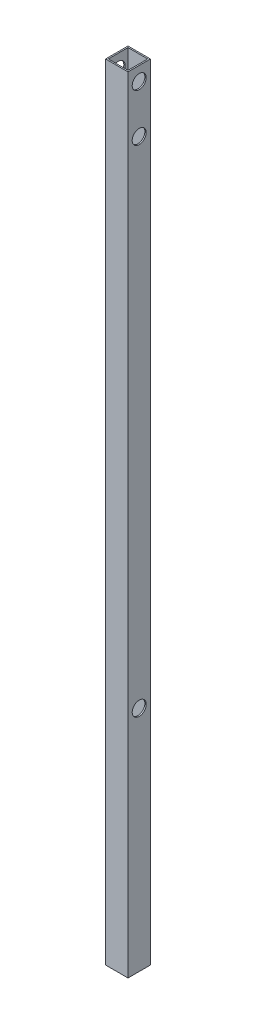
SolidWorks part; units mm, degrees
ref_plane "Front Plane" through (0, 0, 0) normal (0, 0, 1) x (1, 0, 0)
ref_plane "Top Plane" through (0, 0, 0) normal (0, 1, 0) x (1, 0, 0)
ref_plane "Right Plane" through (0, 0, 0) normal (1, 0, 0) x (0, 0, -1)
sketch "Sketch1" plane through (0, 0, 0) normal (0, 1, 0) x (1, 0, 0)
  line L1 (-59.3551, 50.3766) -> (-33.9551, 50.3766)
  line L2 (-59.3551, 50.3766) -> (-59.3551, 24.9766)
  line L3 (-59.3551, 24.9766) -> (-33.9551, 24.9766)
  line L4 (-33.9551, 50.3766) -> (-33.9551, 24.9766)
  line L5 (-57.8311, 48.8526) -> (-35.4791, 48.8526)
  line L6 (-57.8311, 48.8526) -> (-57.8311, 26.5006)
  line L7 (-57.8311, 26.5006) -> (-35.4791, 26.5006)
  line L8 (-35.4791, 48.8526) -> (-35.4791, 26.5006)
  dimension "D1" = 25.4
  dimension "D2" = 25.4
  dimension "D3" = 1.524
  dimension "D4" = 1.524
  dimension "D5" = 1.524
  dimension "D6" = 1.524
extrude "Boss-Extrude1" add sketch "Sketch1" along normal blind 889
sketch "Sketch5" plane through (-33.9551, 0, 0) normal (1, 0, 0) x (0, 0, -1)
  line L0 (50.3766, 889) -> (50.3766, 0) construction
  line L1 (24.9766, 0) -> (50.3766, 0) construction
  circle A0 centre (37.6766, 258.318) radius 7.9375
  dimension "D1" = 15.875
  dimension "D2" = 12.7
  dimension "D3" = 258.318
extrude "Cut-Extrude3" cut sketch "Sketch5" against normal through all both and the other way through all
sketch "Sketch6" plane through (-33.9551, 0, 0) normal (1, 0, 0) x (0, 0, -1)
  line L0 (24.9766, 889) -> (50.3766, 889) construction
  line L1 (50.3766, 889) -> (50.3766, 0) construction
  circle A0 centre (37.6766, 873.125) radius 7.9375
  circle A1 centre (37.6766, 819.277) radius 7.9375
  dimension "D1" = 15.875
  dimension "D2" = 15.875
  dimension "D3" = 15.875
  dimension "D4" = 53.848
  dimension "D5" = 12.7
  dimension "D6" = 12.7
extrude "Cut-Extrude4" cut sketch "Sketch6" against normal through all both and the other way through all
